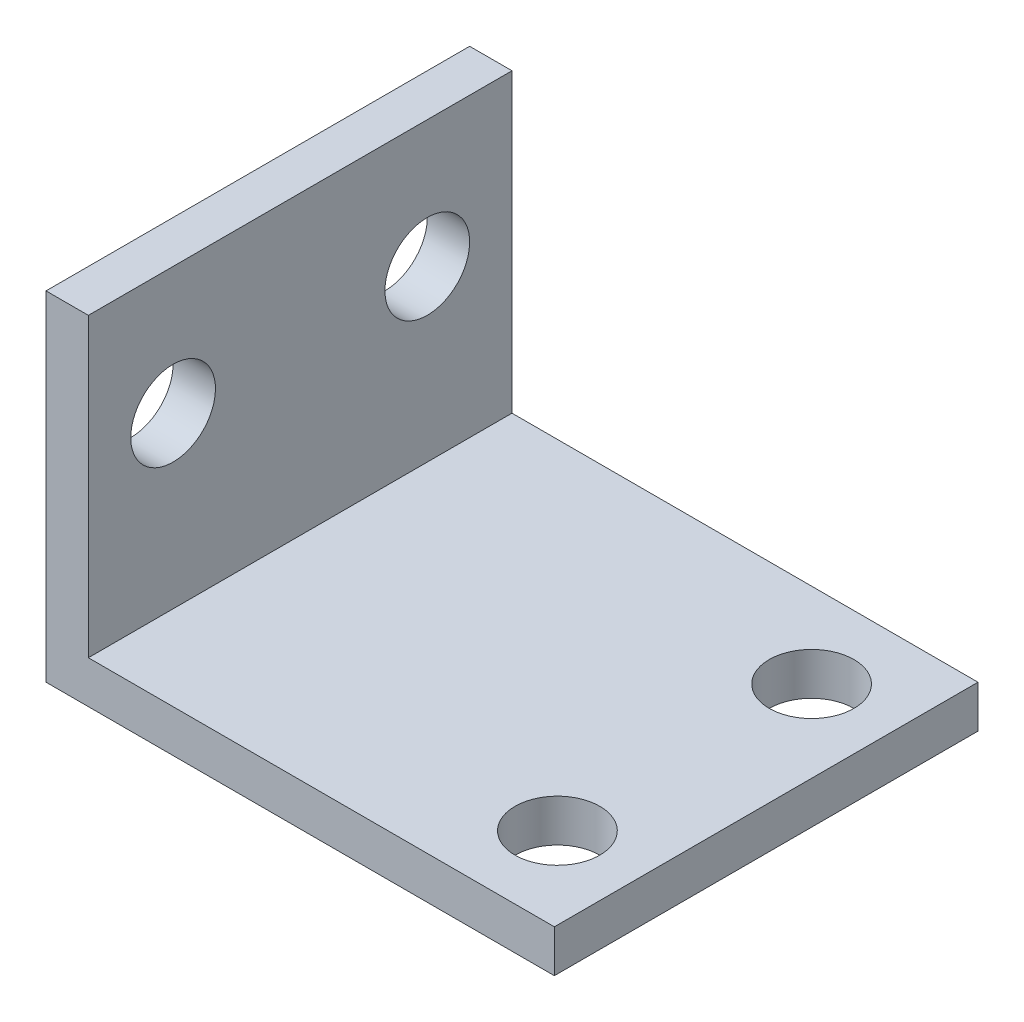
SolidWorks part; units mm, degrees
ref_plane "Front Plane" through (0, 0, 0) normal (0, 0, 1) x (1, 0, 0)
ref_plane "Top Plane" through (0, 0, 0) normal (0, 1, 0) x (1, 0, 0)
ref_plane "Right Plane" through (0, 0, 0) normal (1, 0, 0) x (0, 0, -1)
sketch "Sketch1" plane through (0, 0, 0) normal (0, 0, 1) x (1, 0, 0)
  line L0 (0, 0) -> (0, 25.4)
  line L1 (0, 25.4) -> (3.175, 25.4)
  line L2 (3.175, 25.4) -> (3.175, 3.175)
  line L3 (3.175, 3.175) -> (38.1, 3.175)
  line L4 (38.1, 3.175) -> (38.1, 0)
  line L5 (38.1, 0) -> (0, 0)
  dimension "D1" = 3.175
  dimension "D2" = 3.175
  dimension "D3" = 38.1
  dimension "D4" = 25.4
extrude "Boss-Extrude1" add sketch "Sketch1" along normal blind 31.75
sketch "Sketch2" plane through (0, 3.175, 0) normal (0, 1, 0) x (1, 0, 0)
  line L0 (38.1, -15.875) -> (3.175, -15.875) construction
  line L1 (38.1, -31.75) -> (38.1, 0) construction
  line L2 (3.175, -31.75) -> (3.175, 0) construction
  circle A0 centre (31.9786, -6.35) radius 3.175
  circle A1 centre (31.9786, -25.4) radius 3.175
  point P12 (32.6887, -19.1551)
  point P13 (0, 0)
  dimension "D1" = 6.35
  dimension "D3" = 19.05
  dimension "D2" = 19.05
  dimension "D4" = 31.9786
extrude "Cut-Extrude1" cut sketch "Sketch2" against normal through all
sketch "Sketch3" plane through (3.175, 0, 0) normal (1, 0, 0) x (0, 0, -1)
  line L0 (-15.875, 25.4) -> (-15.875, 3.175) construction
  line L1 (-31.75, 25.4) -> (0, 25.4) construction
  line L2 (-31.75, 3.175) -> (0, 3.175) construction
  line L3 (-31.75, 0) -> (0, 0) construction
  circle A0 centre (-25.4, 15.875) radius 3.175
  circle A1 centre (-6.35, 15.875) radius 3.175
  dimension "D1" = 6.35
  dimension "D2" = 19.05
  dimension "D3" = 15.875
  dimension "D4" = 19.05
extrude "Cut-Extrude2" cut sketch "Sketch3" against normal through all
